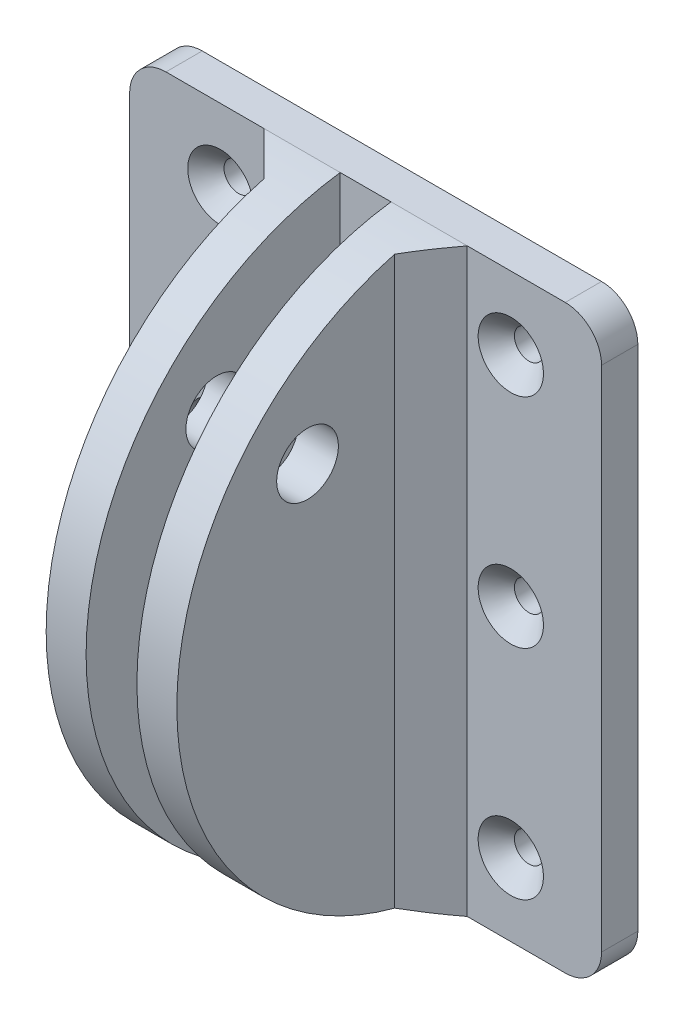
SolidWorks part; units mm, degrees
ref_plane "Front" through (0, 0, 0) normal (0, 0, 1) x (1, 0, 0)
ref_plane "Top" through (0, 0, 0) normal (0, 1, 0) x (1, 0, 0)
ref_plane "Right" through (0, 0, 0) normal (1, 0, 0) x (0, 0, -1)
sketch "Esquisse1" plane through (0, 0, 0) normal (0, 0, 1) x (1, 0, 0)
  line L1 (0, 0) -> (65, 0)
  line L2 (0, 0) -> (0, 80)
  line L3 (0, 80) -> (65, 80)
  line L4 (65, 0) -> (65, 80)
  dimension "D1" = 65
  dimension "D2" = 80
extrude "Boss.-Extru.1" add sketch "Esquisse1" along normal blind 5
sketch "Esquisse2" plane through (0, 0, 5) normal (0, 0, 1) x (1, 0, 0)
  line L0 (32.5, 0) -> (32.5, 80) construction
  line L1 (0, 0) -> (65, 0) construction
  line L2 (65, 80) -> (0, 80) construction
  line L3 (32.5, 40) -> (0, 40) construction
  line L4 (0, 80) -> (0, 0) construction
  line L5 (12.5, 40) -> (12.5, 70) construction
  line L6 (52.5, 40) -> (52.5, 70) construction
  circle A0 centre (12.5, 70) radius 2
  circle A1 centre (12.5, 10) radius 2
  circle A2 centre (12.5, 40) radius 2
  circle A3 centre (52.5, 40) radius 2
  circle A4 centre (52.5, 10) radius 2
  circle A5 centre (52.5, 70) radius 2
  dimension "D1" = 4
  dimension "D2" = 40
  dimension "D3" = 30
extrude "Enlèv. mat.-Extru.1" cut sketch "Esquisse2" against normal through all both and the other way through all
sketch "Esquisse3" plane through (0, 0, 5) normal (0, 0, 1) x (1, 0, 0)
  line L0 (32.5, 0) -> (32.5, 80) construction
  line L1 (0, 0) -> (65, 0) construction
  line L2 (65, 80) -> (0, 80) construction
  line L3 (41.5, 80) -> (23.5, 80)
  line L4 (23.5, 80) -> (23.5, 0)
  line L5 (23.5, 0) -> (41.5, 0)
  line L6 (41.5, 80) -> (41.5, 0)
  dimension "D1" = 18
extrude "Boss.-Extru.2" add sketch "Esquisse3" along normal blind 35
sketch "Esquisse4" plane through (23.5, 0, 0) normal (-1, 0, 0) x (0, 0, 1)
  line L0 (40, 80) -> (40, 0) construction
  line L1 (5, 80) -> (41, 80)
  line L2 (41, 80) -> (41, 0)
  line L3 (41, 0) -> (5, 0)
  arc A0 (5, 0) -> (5, 80) centre (-0.3571, 40) ccw
  dimension "D1" = 1
extrude "Enlèv. mat.-Extru.2" cut sketch "Esquisse4" against normal through all both and the other way through all
sketch "Esquisse5" plane through (23.5, 0, 0) normal (-1, 0, 0) x (0, 0, 1)
  line L0 (5, 80) -> (5, 0) construction
  line L1 (5, 80) -> (0, 80) construction
  circle A0 centre (22, 60) radius 4.25
  point P6 (2.5, 80)
  dimension "D1" = 8.5
  dimension "D2" = 17
  dimension "D3" = 20
extrude "Enlèv. mat.-Extru.3" cut sketch "Esquisse5" against normal through all both and the other way through all
sketch "Esquisse6" plane through (0, 0, 5) normal (0, 0, 1) x (1, 0, 0)
  line L0 (32.5, 0) -> (32.5, 80) construction
  line L1 (41.5, 0) -> (23.5, 0) construction
  line L2 (41.5, 80) -> (23.5, 80) construction
  line L3 (36, 80) -> (29, 80)
  line L4 (29, 80) -> (29, 0)
  line L5 (29, 0) -> (36, 0)
  line L6 (36, 80) -> (36, 0)
  dimension "D1" = 7
extrude "Enlèv. mat.-Extru.4" cut sketch "Esquisse6" along normal through all
chamfer "Chanfrein1" distance 5 angle 45 2 edges at (41.5, 40, 5) (23.5, 40, 5)
chamfer "Chanfrein2" distance 2.5 angle 45 6 edges at (50.5, 70, 5) (50.5, 40, 5) (50.5, 10, 5) (10.5, 10, 5) (10.5, 40, 5) (10.5, 70, 5)
fillet "Congé1" radius 5 4 edges at (0, 80, 2.5) (65, 80, 2.5) (65, 0, 2.5) (0, 0, 2.5)
